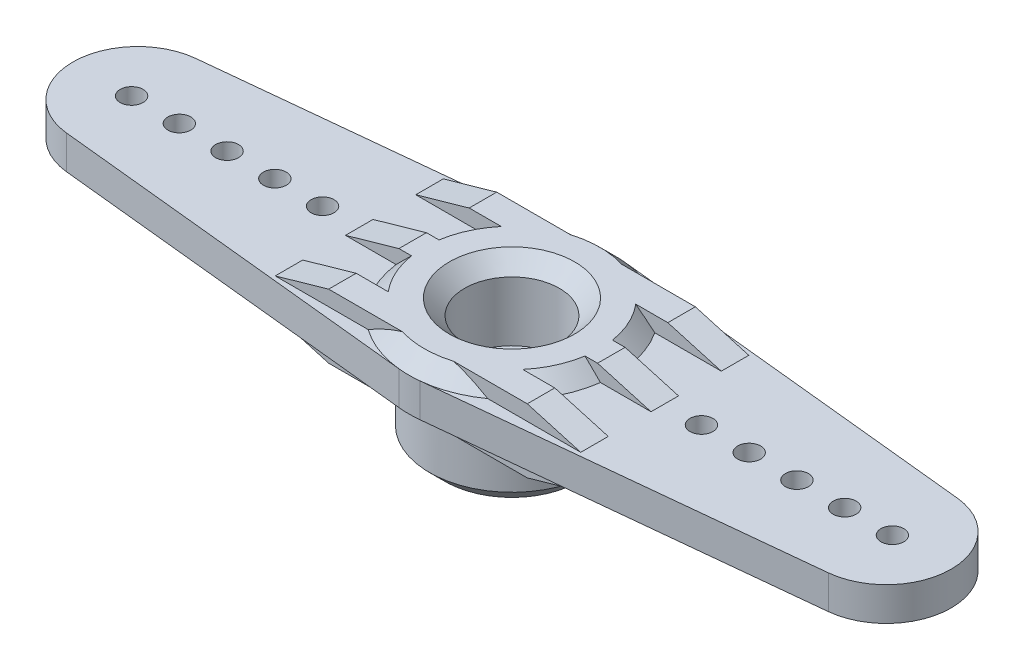
SolidWorks part; units mm, degrees
material "ABS"
ref_plane "Plan de face" through (0, 0, 0) normal (0, 0, 1) x (1, 0, 0)
ref_plane "Plan de dessus" through (0, 0, 0) normal (0, 1, 0) x (1, 0, 0)
ref_plane "Plan de droite" through (0, 0, 0) normal (1, 0, 0) x (0, 0, -1)
sketch "Esquisse1" plane through (0, 0, 0) normal (0, 1, 0) x (1, 0, 0)
  line L0 (0, 14.1765) -> (0, -12.8514) construction
  line L1 (-24.9337, 4.2278) -> (-0.6888, 6.7148)
  line L2 (-24.9337, -4.2278) -> (-0.6888, -6.7148)
  line L3 (-24.9, 0) -> (-21.775, 0) construction
  line L4 (-21.775, 0) -> (-18.65, 0) construction
  line L5 (-18.65, 0) -> (-15.525, 0) construction
  line L6 (-15.525, 0) -> (-12.4, 0) construction
  line L7 (-28.75, 0) -> (28.75, 0) construction
  line L8 (24.9337, -4.2278) -> (0.6888, -6.7148)
  line L9 (24.9337, 4.2278) -> (0.6888, 6.7148)
  circle A0 centre (0, 0) radius 1.75
  arc A1 (0.6888, 6.7148) -> (-0.6888, 6.7148) centre (0, 0) ccw
  arc A2 (-24.9337, -4.2278) -> (-24.9337, 4.2278) centre (-24.5, 0) cw
  circle A3 centre (-24.9, 0) radius 0.75
  circle A4 centre (-21.775, 0) radius 0.75
  circle A5 centre (-18.65, 0) radius 0.75
  circle A6 centre (-15.525, 0) radius 0.75
  circle A7 centre (-12.4, 0) radius 0.75
  arc A8 (0.6888, -6.7148) -> (-0.6888, -6.7148) centre (0, 0) cw
  arc A9 (24.9337, -4.2278) -> (24.9337, 4.2278) centre (24.5, 0) ccw
  circle A10 centre (24.9, 0) radius 0.75
  circle A11 centre (21.775, 0) radius 0.75
  circle A12 centre (18.65, 0) radius 0.75
  circle A13 centre (15.525, 0) radius 0.75
  circle A14 centre (12.4, 0) radius 0.75
  dimension "D1" = 3.5
  dimension "D2" = 6.75
  dimension "D4" = 49.8
  dimension "D5" = 1.5
  dimension "D7" = 4.25
  dimension "D3" = 57.5
  dimension "D6" = 12.4
extrude "Extrusion1" add sketch "Esquisse1" along normal blind 2.2
sketch "Esquisse2" plane through (0, 0, 0) normal (0, -1, 0) x (1, 0, 0)
  circle A0 centre (0, 0) radius 1.75 construction
  circle A1 centre (0, 0) radius 5.4
  circle A3 centre (0, 0) radius 1.75
  dimension "D2" = 10.8
extrude "Extrusion2" add sketch "Esquisse2" along normal blind 5
sketch "Esquisse3" plane through (0, 2.2, 0) normal (0, 1, 0) x (1, 0, 0)
  circle A0 centre (0, 0) radius 3.1
  dimension "D1" = 6.2
extrude "Extrusion3" cut sketch "Esquisse3" against normal blind 3.9
sketch "Esquisse4" plane through (0, -5, 0) normal (0, -1, 0) x (1, 0, 0)
  circle A0 centre (0, 0) radius 2.9
  dimension "D1" = 5.8
extrude "Extrusion4" cut sketch "Esquisse4" against normal blind 3.2
sketch "Esquisse5" plane through (0, 2.2, 0) normal (0, 1, 0) x (1, 0, 0)
  circle A0 centre (0, 0) radius 3.1 construction
  circle A1 centre (0, 0) radius 6.75
  arc A2 (-0.6888, -6.7148) -> (0.6888, -6.7148) centre (0, 0) ccw construction
  circle A3 centre (0, 0) radius 3.1
extrude "Extrusion5" add sketch "Esquisse5" along normal blind 1
chamfer "Chanfrein1" distance 1 angle 45 3 edges at (0, -5, -5.4) (0, 3.2, 3.1) (0, 3.2, 6.75)
sketch "Esquisse6" plane through (0, 2.2, 0) normal (0, 1, 0) x (1, 0, 0)
  line L0 (11.0958, 0) -> (-14.2966, 0) construction
  line L1 (10, -5.5) -> (-10, -5.5)
  line L2 (10, -5.5) -> (10, -3.7)
  line L3 (10, -3.7) -> (3.363, -3.7)
  line L4 (-10, -5.5) -> (-10, -3.7)
  line L5 (10, -0.9) -> (4.9183, -0.9)
  line L6 (10, -0.9) -> (10, 0.9)
  line L7 (10, 0.9) -> (4.9183, 0.9)
  line L8 (-10, -0.9) -> (-10, 0.9)
  line L9 (0, -10.3407) -> (0, 10.3407) construction
  line L10 (10, 3.7) -> (3.363, 3.7)
  line L11 (10, 3.7) -> (10, 5.5)
  line L12 (10, 5.5) -> (-10, 5.5)
  line L13 (-10, 3.7) -> (-10, 5.5)
  line L14 (-3.363, -3.7) -> (-10, -3.7)
  line L15 (-4.9183, -0.9) -> (-10, -0.9)
  line L16 (-4.9183, 0.9) -> (-10, 0.9)
  line L17 (-3.363, 3.7) -> (-10, 3.7)
  arc A0 (-3.363, -3.7) -> (3.363, -3.7) centre (0, 0) ccw
  arc A1 (4.9183, -0.9) -> (4.9183, 0.9) centre (0, 0) ccw
  arc A2 (3.363, 3.7) -> (-3.363, 3.7) centre (0, 0) ccw
  arc A3 (-4.9183, 0.9) -> (-4.9183, -0.9) centre (0, 0) ccw
  dimension "D4" = 10
  dimension "D1" = 20
  dimension "D2" = 1.8
  dimension "D3" = 11
extrude "Extrusion6" add sketch "Esquisse6" along normal blind 1 and the other way blind 3.2
chamfer "Chanfrein2" distance 1 distance2 3.5 6 edges at (-10, 3.2, 4.6) (-10, 3.2, 0) (-10, 3.2, -4.6) (10, 3.2, -4.6) (10, 3.2, 0) (10, 3.2, 4.6) first distance on face at (-10, 2.7, 4.6) first distance on face at (-10, 2.7, 0) first distance on face at (-10, 2.7, -4.6) first distance on face at (10, 2.7, -4.6) first distance on face at (10, 2.7, 0) first distance on face at (10, 2.7, 4.6)
chamfer "Chanfrein3" distance 3.5 distance2 1 6 edges at (10, -1, -4.6) (10, -1, 0) (10, -1, 4.6) (-10, -1, 4.6) (-10, -1, 0) (-10, -1, -4.6) first distance on face at (0, -1, -4.5833) first distance on face at (7.6811, -1, 0) first distance on face at (0, -1, 4.5833) first distance on face at (-7.6811, -1, 0)
